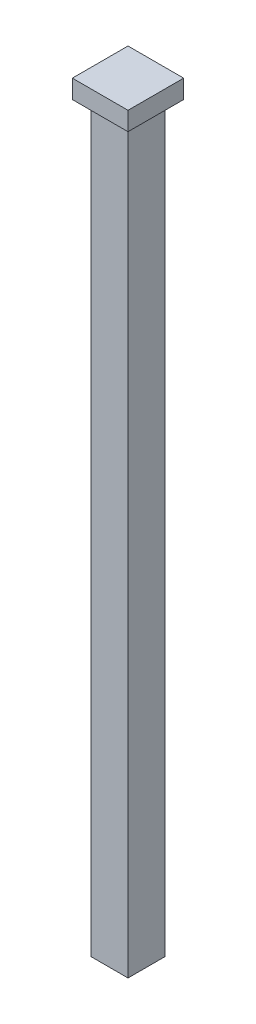
SolidWorks part; units mm, degrees
ref_plane "Front Plane" through (0, 0, 0) normal (0, 0, 1) x (1, 0, 0)
ref_plane "Top Plane" through (0, 0, 0) normal (0, 1, 0) x (1, 0, 0)
ref_plane "Right Plane" through (0, 0, 0) normal (1, 0, 0) x (0, 0, -1)
other "Center of Mass"
ref_axis "Link_3_Axis" through (0, 100, 0) along (0, -1, 0)
sketch "Sketch1" plane through (0, 0, 0) normal (0, 1, 0) x (1, 0, 0)
  line L1 (-75, 75) -> (75, 75)
  line L2 (-75, 75) -> (-75, -75)
  line L3 (-75, -75) -> (75, -75)
  line L4 (75, 75) -> (75, -75)
  line L5 (-75, 75) -> (75, -75) construction
  line L6 (-75, -75) -> (75, 75) construction
  point P0 (0, 0)
  dimension "D1" = 150
  dimension "D2" = 150
extrude "Boss-Extrude1" add sketch "Sketch1" along normal blind 50
sketch "Sketch2" plane through (0, 0, 0) normal (0, -1, 0) x (1, 0, 0)
  line L1 (-50, 50) -> (50, 50)
  line L2 (-50, 50) -> (-50, -50)
  line L3 (-50, -50) -> (50, -50)
  line L4 (50, 50) -> (50, -50)
  line L5 (-50, 50) -> (50, -50) construction
  line L6 (-50, -50) -> (50, 50) construction
  point P0 (0, 0)
  dimension "D1" = 100
  dimension "D2" = 100
extrude "Boss-Extrude2" add sketch "Sketch2" along normal blind 2000
sketch "Sketch3" plane through (0, -2000, 0) normal (0, -1, 0) x (1, 0, 0)
  circle A0 centre (0, 0) radius 25
  dimension "D1" = 50
extrude "Cut-Extrude1" cut sketch "Sketch3" against normal blind 25
